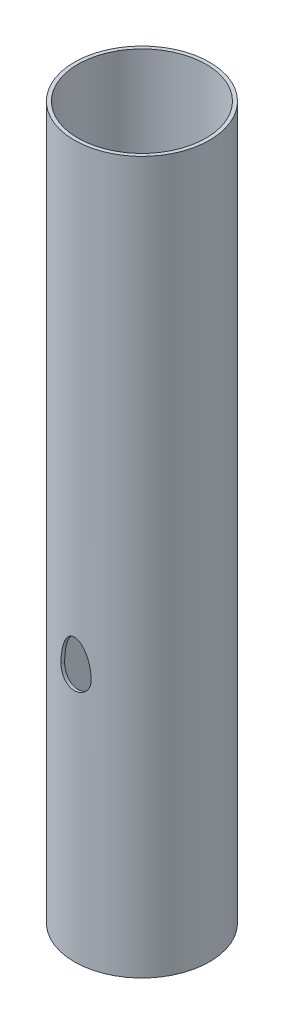
SolidWorks part; units mm, degrees
ref_plane "Front Plane" through (0, 0, 0) normal (0, 0, 1) x (1, 0, 0)
ref_plane "Top Plane" through (0, 0, 0) normal (0, 1, 0) x (1, 0, 0)
ref_plane "Right Plane" through (0, 0, 0) normal (1, 0, 0) x (0, 0, -1)
sketch "Sketch2" plane through (0, 0, 0) normal (0, 1, 0) x (1, 0, 0)
  circle A0 centre (0, 0) radius 36
  circle A1 centre (0, 0) radius 38
  dimension "D1" = 2
  dimension "D2" = 76
extrude "Boss-Extrude1" add sketch "Sketch2" along normal blind 400
ref_axis "Axis1" through (41.8, 0, 0) along (-1, 0, 0)
ref_plane "Plane1" through (0, 0, 0) normal (0, 0.2045, 0.9789) x (-1, 0, 0)
sketch "Sketch3" plane through (0, 0, 0) normal (0, 0.2045, 0.9789) x (-1, 0, 0)
  line L0 (0, 41.8) -> (0, -41.8) construction
  line L2 (-41.8, 0) -> (41.8, 0) construction
  arc A0 (8.5, -130) -> (-8.5, -130) centre (0, -130) ccw
  arc A1 (-8.5, -130) -> (8.5, -130) centre (0, -130) ccw construction
  ellipse E0 centre (0, -130) end of major axis (0, -147) minor radius 8.5 (-8.5, -130) -> (8.5, -130) ccw
  dimension "D1" = 17
  dimension "D2" = 130
  dimension "D3" = 17
extrude "Cut-Extrude1" cut sketch "Sketch3" along normal up to next
